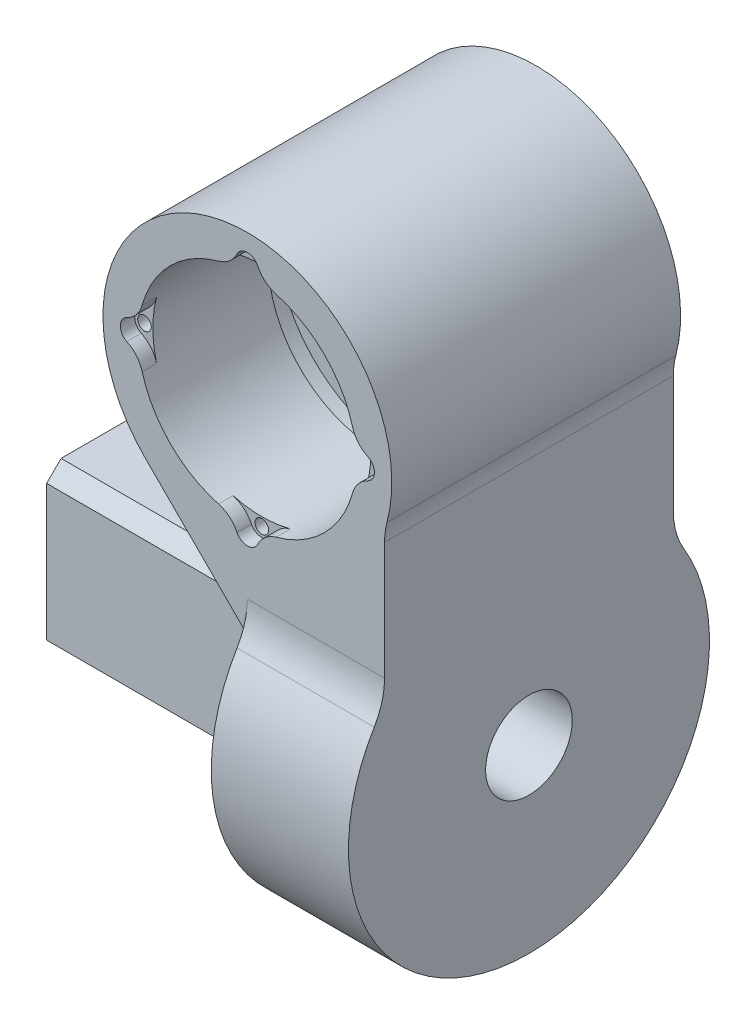
SolidWorks part; units mm, degrees
ref_plane "Front Plane" through (0, 0, 0) normal (0, 0, 1) x (1, 0, 0)
ref_plane "Top Plane" through (0, 0, 0) normal (0, 1, 0) x (1, 0, 0)
ref_plane "Right Plane" through (0, 0, 0) normal (1, 0, 0) x (0, 0, -1)
sketch "Sketch1" plane through (0, 0, 0) normal (1, 0, 0) x (0, 0, -1)
  circle A0 centre (0, 0) radius 62.5
  circle A1 centre (0, 0) radius 15
  dimension "D1" = 125
  dimension "D2" = 30
extrude "Boss-Extrude1" add sketch "Sketch1" along normal blind 47.5
sketch "Sketch2" plane through (0, 0, 0) normal (0, 0, 1) x (1, 0, 0)
  line L1 (0, 0) -> (0, 105) construction
  line L2 (-35.3553, 69.6447) -> (0, 34.2893)
  line L3 (0, 34.2893) -> (0, 55)
  arc A0 (0, 55) -> (-35.3553, 69.6447) centre (0, 105) ccw
  circle A1 centre (0, 105) radius 32.5
  arc A2 (-35.3553, 69.6447) -> (0, 55) centre (0, 105) ccw construction
  dimension "D1" = 100
  dimension "D2" = 65
  dimension "D3" = 105
  dimension "D4" = 45
extrude "Boss-Extrude2" add sketch "Sketch2" along normal mid plane 100
sketch "Sketch3" plane through (47.5, 0, 0) normal (1, 0, 0) x (0, 0, -1)
  line L0 (-50, 55) -> (-50, 62.5)
  line L1 (-50, 155) -> (-50, 55) construction
  line L2 (-50, 55) -> (-50, 37.5)
  line L3 (-29.6859, 55) -> (-50, 55)
  line L4 (-50, 55) -> (-50, 37.5)
  line L6 (50, 55) -> (29.6859, 55)
  line L7 (50, 37.5) -> (50, 55)
  line L9 (50, 37.5) -> (50, 55)
  line L10 (-50, 62.5) -> (50, 62.5)
  line L11 (50, 55) -> (50, 155) construction
  line L12 (50, 62.5) -> (50, 55)
  line L13 (29.6859, 55) -> (-29.6859, 55)
  circle A0 centre (0, 0) radius 62.5 construction
  arc A1 (-29.6859, 55) -> (-50, 37.5) centre (0, 0) ccw
  arc A2 (-29.6859, 55) -> (-50, 37.5) centre (0, 0) ccw
  arc A3 (50, 37.5) -> (29.6859, 55) centre (0, 0) ccw
  arc A4 (50, 37.5) -> (29.6859, 55) centre (0, 0) ccw
  dimension "D1" = 0
  dimension "D2" = 0
extrude "Boss-Extrude3" add sketch "Sketch3" against normal up to surface (47.5 mm away) up to face at (0, 49.5341, 43.5451)
sketch "Sketch4" plane through (0, 0, 50) normal (0, 0, 1) x (1, 0, 0)
  line L0 (47.5, 62.5) -> (47.5, 89.3875)
  line L1 (26.3391, 62.5) -> (47.5, 62.5) construction
  line L2 (26.3391, 62.5) -> (47.5, 62.5)
  arc A0 (26.3391, 62.5) -> (-35.3553, 69.6447) centre (0, 105) ccw construction
  arc A1 (26.3391, 62.5) -> (-35.3553, 69.6447) centre (0, 105) ccw
  line M2 (47.5, 62.5) -> (26.3391, 62.5)
  arc M3 (26.3391, 62.5) -> (-35.3553, 69.6447) centre (0, 105) ccw
extrude "Boss-Extrude4" add sketch "Sketch4" against normal up to surface (100 mm away) contours L0 M2 M3 region at (41.2754, 70.2611, 50) up to face at (16.0406, 65.4216, -50)
fillet "Fillet1" radius 25 3 edges at (23.75, 37.5, -50) (23.75, 37.5, 50) (47.5, 89.3875, 0)
sketch "Sketch5" plane through (0, 0, 0) normal (-1, 0, 0) x (0, 0, 1)
  line L1 (-28.5, -28.5) -> (28.5, -28.5)
  line L2 (-28.5, -28.5) -> (-28.5, 28.5)
  line L3 (-28.5, 28.5) -> (28.5, 28.5)
  line L4 (28.5, -28.5) -> (28.5, 28.5)
  line L5 (-28.5, -28.5) -> (28.5, 28.5) construction
  line L6 (-28.5, 28.5) -> (28.5, -28.5) construction
  point P0 (0, 0)
  dimension "D1" = 57
extrude "Boss-Extrude5" add sketch "Sketch5" along normal blind 91
chamfer "Chamfer1" distance 5 angle 45 4 edges at (-45.5, -28.5, 28.5) (-45.5, -28.5, -28.5) (-45.5, 28.5, 28.5) (-45.5, 28.5, -28.5)
sketch "Sketch6" plane through (0, 0, 50) normal (0, 0, 1) x (1, 0, 0)
  circle A0 centre (0, 105) radius 37.75
  dimension "D1" = 75.5
extrude "Cut-Extrude1" cut sketch "Sketch6" against normal up to surface (100 mm away) up to face at (14.7119, 74.0752, -50)
ref_plane "Plane1" through (0, 0, 0) normal (0, 0, 1) x (1, 0, 0)
sketch "Sketch8" plane through (0, 0, 0) normal (0, 0, 1) x (1, 0, 0)
  circle A0 centre (0, 105) radius 45
  dimension "D1" = 90
extrude "Cut-Extrude2" cut sketch "Sketch8" against normal blind 5 and the other way blind 5
ref_plane "Plane2" through (0, 0, -40) normal (0, 0, -1) x (-1, 0, 0)
sketch "Sketch9" plane through (0, 0, -40) normal (0, 0, -1) x (-1, 0, 0)
  circle A0 centre (0, 105) radius 45
  dimension "D1" = 90
extrude "Cut-Extrude3" cut sketch "Sketch9" against normal blind 5 and the other way blind 5
sketch "Sketch10" plane through (0, 0, 50) normal (0, 0, 1) x (1, 0, 0)
  line L0 (0, 105) -> (0, 165.1178) construction
  line L1 (4, 157.8762) -> (4, 137.7793) construction
  line L2 (-4, 159.0998) -> (-4, 137.2973) construction
  line L3 (-4, 145) -> (4, 145) construction
  line L4 (-4, 142.3994) -> (-4, 145)
  line L5 (4, 145) -> (4, 142.4872)
  arc A1 (-4, 145) -> (4, 145) centre (0, 145) cw
  arc A3 (-4, 142.3994) -> (4, 142.4872) centre (0.2897, 116.045) cw
  dimension "D1" = 40
  dimension "D2" = 4
  dimension "D3" = 4
extrude "Cut-Extrude4" cut sketch "Sketch10" against normal blind 5
fillet "Fillet2" radius 10 2 edges at (-4, 142.5375, 47.5) (4, 142.5375, 47.5)
pattern_circular "CirPattern1" count 4 over 360 about axis through (0, 105, 50) along (0, 0, 1) of "Cut-Extrude4", "Fillet2"
sketch "Sketch11" plane through (0, 0, 45) normal (0, 0, 1) x (1, 0, 0)
  circle A0 centre (0, 145.621) radius 2.35
  circle A1 centre (40.621, 105) radius 2.35
  circle A2 centre (0, 64.379) radius 2.35
  circle A3 centre (-40.621, 105) radius 2.35
  point P11 (0, 105)
  dimension "D1" = 4.7
  dimension "D2" = 4
extrude "Cut-Extrude5" cut sketch "Sketch11" against normal blind 4
sketch "Sketch12" plane through (0, 0, 41) normal (0, 0, 1) x (1, 0, 0)
  circle A0 centre (0, 145.621) radius 1.75
  circle A1 centre (40.621, 105) radius 1.75
  circle A2 centre (0, 64.379) radius 1.75
  circle A3 centre (-40.621, 105) radius 1.75
  point P12 (0, 105)
  dimension "D1" = 3.5
  dimension "D2" = 4
extrude "Cut-Extrude6" cut sketch "Sketch12" against normal blind 4
